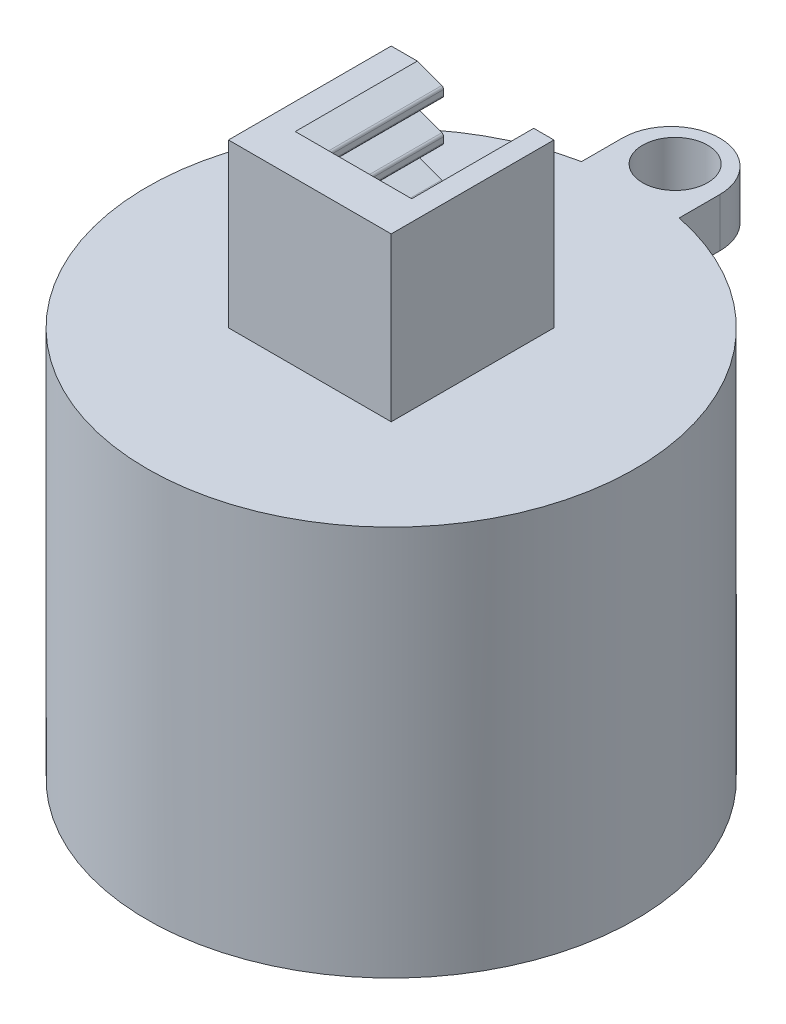
SolidWorks part; units mm, degrees
ref_plane "Front Plane" through (0, 0, 0) normal (0, 0, 1) x (1, 0, 0)
ref_plane "Top Plane" through (0, 0, 0) normal (0, 1, 0) x (1, 0, 0)
ref_plane "Right Plane" through (0, 0, 0) normal (1, 0, 0) x (0, 0, -1)
sketch "Sketch1" plane through (0, 0, 0) normal (0, 1, 0) x (1, 0, 0)
  circle A0 centre (0, 0) radius 15
  circle A1 centre (0, 0) radius 13
  dimension "D1" = 26
  dimension "D2" = 30
extrude "Boss-Extrude1" add sketch "Sketch1" along normal blind 20
sketch "Sketch2" plane through (0, 20, 0) normal (0, 1, 0) x (1, 0, 0)
  circle A0 centre (0, 0) radius 15
extrude "Boss-Extrude2" add sketch "Sketch2" along normal blind 4
sketch "Sketch4" plane through (0, 24, 0) normal (0, 1, 0) x (1, 0, 0)
  line L0 (0, 5) -> (0, -5) construction
  line L1 (-5, 5) -> (5, 5)
  line L2 (-5, 5) -> (-5, -5)
  line L3 (-5, -5) -> (5, -5)
  line L4 (5, 5) -> (5, -5)
  line L5 (-5, 0) -> (5, 0) construction
  dimension "D1" = 10
  dimension "D2" = 10
extrude "Boss-Extrude3" add sketch "Sketch4" along normal blind 10
sketch "Sketch6" plane through (0, 0, -5) normal (0, 0, -1) x (-1, 0, 0)
  line L1 (-5, 34) -> (5, 34) construction
  line L3 (-3.7584, 34) -> (3.3958, 34)
  line L4 (-3.7584, 24) -> (3.5416, 24)
  line L405 (2.1355, 274) -> (0.2416, 274)
  line L406 (0.2416, 274) -> (0.2416, 34)
  line L407 (0.2416, 34) -> (-1.7584, 34)
  line L408 (-1.7584, 34) -> (-1.7584, 274)
  line L409 (-1.7584, 274) -> (-3.7584, 274)
  line L410 (-3.7584, 274) -> (-3.7584, 24)
  line L411 (-3.7584, 24) -> (3.5416, 24)
  line L412 (3.5416, 24) -> (3.5416, 24.6743)
  line L413 (3.5416, 24.6743) -> (1.8918, 25.2748)
  line L414 (1.7816, 25.432) -> (1.7816, 25.7555)
  line L415 (1.8918, 25.9128) -> (3.5416, 26.5133)
  line L416 (3.5416, 26.5133) -> (3.5416, 27.1876)
  line L417 (3.5416, 27.1876) -> (1.8918, 27.7881)
  line L418 (1.7816, 27.9453) -> (1.7816, 28.2688)
  line L419 (1.8918, 28.426) -> (3.5416, 29.0265)
  line L420 (3.5416, 29.0265) -> (3.5416, 29.7008)
  line L421 (3.5416, 29.7008) -> (1.8918, 30.3013)
  line L422 (1.7816, 30.4586) -> (1.7816, 30.7821)
  line L423 (1.8918, 30.9393) -> (3.5416, 31.5398)
  line L424 (3.5416, 31.5398) -> (3.5416, 32.2141)
  line L425 (3.5416, 32.2141) -> (1.8918, 32.8146)
  line L426 (1.7816, 32.9719) -> (1.7816, 33.2953)
  line L427 (1.8918, 33.4526) -> (3.5416, 34.0531)
  line L428 (3.5416, 34.0531) -> (3.5416, 34.7274)
  line L429 (3.5416, 34.7274) -> (1.8918, 35.3279)
  line L430 (1.7816, 35.4851) -> (1.7816, 35.8086)
  line L431 (1.8918, 35.9658) -> (3.5416, 36.5664)
  line L432 (3.5416, 36.5664) -> (3.5416, 37.2406)
  line L433 (3.5416, 37.2406) -> (1.8918, 37.8412)
  line L434 (1.7816, 37.9984) -> (1.7816, 38.3219)
  line L435 (1.8918, 38.4791) -> (3.5416, 39.0796)
  line L436 (3.5416, 39.0796) -> (3.5416, 39.7539)
  line L437 (3.5416, 39.7539) -> (1.8918, 40.3544)
  line L438 (1.7816, 40.5117) -> (1.7816, 40.8351)
  line L439 (1.8918, 40.9924) -> (3.5416, 41.5929)
  line L440 (3.5416, 41.5929) -> (3.5416, 42.2672)
  line L441 (3.5416, 42.2672) -> (1.8918, 42.8677)
  line L442 (1.7816, 43.025) -> (1.7816, 43.3484)
  line L443 (1.8918, 43.5057) -> (3.5416, 44.1062)
  line L444 (3.5416, 44.1062) -> (3.5416, 44.7805)
  line L445 (3.5416, 44.7805) -> (1.8918, 45.381)
  line L446 (1.7816, 45.5382) -> (1.7816, 45.8617)
  line L447 (1.8918, 46.0189) -> (3.5416, 46.6194)
  line L448 (3.5416, 46.6194) -> (3.5416, 47.2937)
  line L449 (3.5416, 47.2937) -> (1.8918, 47.8942)
  line L450 (1.7816, 48.0515) -> (1.7816, 48.375)
  line L451 (1.8918, 48.5322) -> (3.5416, 49.1327)
  line L452 (3.5416, 49.1327) -> (3.5416, 49.807)
  line L453 (3.5416, 49.807) -> (1.8918, 50.4075)
  line L454 (1.7816, 50.5648) -> (1.7816, 50.8882)
  line L455 (1.8918, 51.0455) -> (3.5416, 51.646)
  line L456 (3.5416, 51.646) -> (3.5416, 52.3203)
  line L457 (3.5416, 52.3203) -> (1.8918, 52.9208)
  line L458 (1.7816, 53.078) -> (1.7816, 53.4015)
  line L459 (1.8918, 53.5588) -> (3.5416, 54.1593)
  line L460 (3.5416, 54.1593) -> (3.5416, 54.8335)
  line L461 (3.5416, 54.8335) -> (1.8918, 55.4341)
  line L462 (1.7816, 55.5913) -> (1.7816, 55.9148)
  line L463 (1.8918, 56.072) -> (3.5416, 56.6725)
  line L464 (3.5416, 56.6725) -> (3.5416, 57.3468)
  line L465 (3.5416, 57.3468) -> (1.8918, 57.9473)
  line L466 (1.7816, 58.1046) -> (1.7816, 58.428)
  line L467 (1.8918, 58.5853) -> (3.5416, 59.1858)
  line L468 (3.5416, 59.1858) -> (3.5416, 59.8601)
  line L469 (3.5416, 59.8601) -> (1.8918, 60.4606)
  line L470 (1.7816, 60.6179) -> (1.7816, 60.9413)
  line L471 (1.8918, 61.0986) -> (3.5416, 61.6991)
  line L472 (3.5416, 61.6991) -> (3.5416, 62.3734)
  line L473 (3.5416, 62.3734) -> (1.8918, 62.9739)
  line L474 (1.7816, 63.1311) -> (1.7816, 63.4546)
  line L475 (1.8918, 63.6118) -> (3.5416, 64.2124)
  line L476 (3.5416, 64.2124) -> (3.5416, 64.8866)
  line L477 (3.5416, 64.8866) -> (1.8918, 65.4871)
  line L478 (1.7816, 65.6444) -> (1.7816, 65.9679)
  line L479 (1.8918, 66.1251) -> (3.5416, 66.7256)
  line L480 (3.5416, 66.7256) -> (3.5416, 67.3999)
  line L481 (3.5416, 67.3999) -> (1.8918, 68.0004)
  line L482 (1.7816, 68.1577) -> (1.7816, 68.4811)
  line L483 (1.8918, 68.6384) -> (3.5416, 69.2389)
  line L484 (3.5416, 69.2389) -> (3.5416, 69.9132)
  line L485 (3.5416, 69.9132) -> (1.8918, 70.5137)
  line L486 (1.7816, 70.6709) -> (1.7816, 70.9944)
  line L487 (1.8918, 71.1517) -> (3.5416, 71.7522)
  line L488 (3.5416, 71.7522) -> (3.5416, 72.4265)
  line L489 (3.5416, 72.4265) -> (1.8918, 73.027)
  line L490 (1.7816, 73.1842) -> (1.7816, 73.5077)
  line L491 (1.8918, 73.6649) -> (3.5416, 74.2654)
  line L492 (3.5416, 74.2654) -> (3.5416, 74.9397)
  line L493 (3.5416, 74.9397) -> (1.8918, 75.5402)
  line L494 (1.7816, 75.6975) -> (1.7816, 76.0209)
  line L495 (1.8918, 76.1782) -> (3.5416, 76.7787)
  line L496 (3.5416, 76.7787) -> (3.5416, 77.453)
  line L497 (3.5416, 77.453) -> (1.8918, 78.0535)
  line L498 (1.7816, 78.2108) -> (1.7816, 78.5342)
  line L499 (1.8918, 78.6915) -> (3.5416, 79.292)
  line L500 (3.5416, 79.292) -> (3.5416, 79.9663)
  line L501 (3.5416, 79.9663) -> (1.8918, 80.5668)
  line L502 (1.7816, 80.724) -> (1.7816, 81.0475)
  line L503 (1.8918, 81.2047) -> (3.5416, 81.8053)
  line L504 (3.5416, 81.8053) -> (3.5416, 82.4795)
  line L505 (3.5416, 82.4795) -> (1.8918, 83.0801)
  line L506 (1.7816, 83.2373) -> (1.7816, 83.5608)
  line L507 (1.8918, 83.718) -> (3.5416, 84.3185)
  line L508 (3.5416, 84.3185) -> (3.5416, 84.9928)
  line L509 (3.5416, 84.9928) -> (1.8918, 85.5933)
  line L510 (1.7816, 85.7506) -> (1.7816, 86.074)
  line L511 (1.8918, 86.2313) -> (3.5416, 86.8318)
  line L512 (3.5416, 86.8318) -> (3.5416, 87.5061)
  line L513 (3.5416, 87.5061) -> (1.8918, 88.1066)
  line L514 (1.7816, 88.2638) -> (1.7816, 88.5873)
  line L515 (1.8918, 88.7446) -> (3.5416, 89.3451)
  line L516 (3.5416, 89.3451) -> (3.5416, 90.0194)
  line L517 (3.5416, 90.0194) -> (1.8918, 90.6199)
  line L518 (1.7816, 90.7771) -> (1.7816, 91.1006)
  line L519 (1.8918, 91.2578) -> (3.5416, 91.8583)
  line L520 (3.5416, 91.8583) -> (3.5416, 92.5326)
  line L521 (3.5416, 92.5326) -> (1.8918, 93.1331)
  line L522 (1.7816, 93.2904) -> (1.7816, 93.6139)
  line L523 (1.8918, 93.7711) -> (3.5416, 94.3716)
  line L524 (3.5416, 94.3716) -> (3.5416, 95.0459)
  line L525 (3.5416, 95.0459) -> (1.8918, 95.6464)
  line L526 (1.7816, 95.8037) -> (1.7816, 96.1271)
  line L527 (1.8918, 96.2844) -> (3.5416, 96.8849)
  line L528 (3.5416, 96.8849) -> (3.5416, 97.5592)
  line L529 (3.5416, 97.5592) -> (1.8918, 98.1597)
  line L530 (1.7816, 98.3169) -> (1.7816, 98.6404)
  line L531 (1.8918, 98.7976) -> (3.5416, 99.3982)
  line L532 (3.5416, 99.3982) -> (3.5416, 100.0724)
  line L533 (3.5416, 100.0724) -> (1.8918, 100.673)
  line L534 (1.7816, 100.8302) -> (1.7816, 101.1537)
  line L535 (1.8918, 101.3109) -> (3.5416, 101.9114)
  line L536 (3.5416, 101.9114) -> (3.5416, 102.5857)
  line L537 (3.5416, 102.5857) -> (1.8918, 103.1862)
  line L538 (1.7816, 103.3435) -> (1.7816, 103.6669)
  line L539 (1.8918, 103.8242) -> (3.5416, 104.4247)
  line L540 (3.5416, 104.4247) -> (3.5416, 105.099)
  line L541 (3.5416, 105.099) -> (1.8918, 105.6995)
  line L542 (1.7816, 105.8568) -> (1.7816, 106.1802)
  line L543 (1.8918, 106.3375) -> (3.5416, 106.938)
  line L544 (3.5416, 106.938) -> (3.5416, 107.6123)
  line L545 (3.5416, 107.6123) -> (1.8918, 108.2128)
  line L546 (1.7816, 108.37) -> (1.7816, 108.6935)
  line L547 (1.8918, 108.8507) -> (3.5416, 109.4512)
  line L548 (3.5416, 109.4512) -> (3.5416, 110.1255)
  line L549 (3.5416, 110.1255) -> (1.8918, 110.726)
  line L550 (1.7816, 110.8833) -> (1.7816, 111.2068)
  line L551 (1.8918, 111.364) -> (3.5416, 111.9645)
  line L552 (3.5416, 111.9645) -> (3.5416, 112.6388)
  line L553 (3.5416, 112.6388) -> (1.8918, 113.2393)
  line L554 (1.7816, 113.3966) -> (1.7816, 113.72)
  line L555 (1.8918, 113.8773) -> (3.5416, 114.4778)
  line L556 (3.5416, 114.4778) -> (3.5416, 115.1521)
  line L557 (3.5416, 115.1521) -> (1.8918, 115.7526)
  line L558 (1.7816, 115.9098) -> (1.7816, 116.2333)
  line L559 (1.8918, 116.3906) -> (3.5416, 116.9911)
  line L560 (3.5416, 116.9911) -> (3.5416, 117.6653)
  line L561 (3.5416, 117.6653) -> (1.8918, 118.2659)
  line L562 (1.7816, 118.4231) -> (1.7816, 118.7466)
  line L563 (1.8918, 118.9038) -> (3.5416, 119.5043)
  line L564 (3.5416, 119.5043) -> (3.5416, 120.1786)
  line L565 (3.5416, 120.1786) -> (1.8918, 120.7791)
  line L566 (1.7816, 120.9364) -> (1.7816, 121.2598)
  line L567 (1.8918, 121.4171) -> (3.5416, 122.0176)
  line L568 (3.5416, 122.0176) -> (3.5416, 122.6919)
  line L569 (3.5416, 122.6919) -> (1.8918, 123.2924)
  line L570 (1.7816, 123.4497) -> (1.7816, 123.7731)
  line L571 (1.8918, 123.9304) -> (3.5416, 124.5309)
  line L572 (3.5416, 124.5309) -> (3.5416, 125.2052)
  line L573 (3.5416, 125.2052) -> (1.8918, 125.8057)
  line L574 (1.7816, 125.9629) -> (1.7816, 126.2864)
  line L575 (1.8918, 126.4436) -> (3.5416, 127.0442)
  line L576 (3.5416, 127.0442) -> (3.5416, 127.7184)
  line L577 (3.5416, 127.7184) -> (1.8918, 128.3189)
  line L578 (1.7816, 128.4762) -> (1.7816, 128.7997)
  line L579 (1.8918, 128.9569) -> (3.5416, 129.5574)
  line L580 (3.5416, 129.5574) -> (3.5416, 130.2317)
  line L581 (3.5416, 130.2317) -> (1.8918, 130.8322)
  line L582 (1.7816, 130.9895) -> (1.7816, 131.3129)
  line L583 (1.8918, 131.4702) -> (3.5416, 132.0707)
  line L584 (3.5416, 132.0707) -> (3.5416, 132.745)
  line L585 (3.5416, 132.745) -> (1.8918, 133.3455)
  line L586 (1.7816, 133.5027) -> (1.7816, 133.8262)
  line L587 (1.8918, 133.9835) -> (3.5416, 134.584)
  line L588 (3.5416, 134.584) -> (3.5416, 135.2583)
  line L589 (3.5416, 135.2583) -> (1.8918, 135.8588)
  line L590 (1.7816, 136.016) -> (1.7816, 136.3395)
  line L591 (1.8918, 136.4967) -> (3.5416, 137.0972)
  line L592 (3.5416, 137.0972) -> (3.5416, 137.7715)
  line L593 (3.5416, 137.7715) -> (1.8918, 138.372)
  line L594 (1.7816, 138.5293) -> (1.7816, 138.8527)
  line L595 (1.8918, 139.01) -> (3.5416, 139.6105)
  line L596 (3.5416, 139.6105) -> (3.5416, 140.2848)
  line L597 (3.5416, 140.2848) -> (1.8918, 140.8853)
  line L598 (1.7816, 141.0426) -> (1.7816, 141.366)
  line L599 (1.8918, 141.5233) -> (3.5416, 142.1238)
  line L600 (3.5416, 142.1238) -> (3.5416, 142.7981)
  line L601 (3.5416, 142.7981) -> (1.8918, 143.3986)
  line L602 (1.7816, 143.5558) -> (1.7816, 143.8793)
  line L603 (1.8918, 144.0365) -> (3.5416, 144.6371)
  line L604 (3.5416, 144.6371) -> (3.5416, 145.3113)
  line L605 (3.5416, 145.3113) -> (1.8918, 145.9119)
  line L606 (1.7816, 146.0691) -> (1.7816, 146.3926)
  line L607 (1.8918, 146.5498) -> (3.5416, 147.1503)
  line L608 (3.5416, 147.1503) -> (3.5416, 147.8246)
  line L609 (3.5416, 147.8246) -> (1.8918, 148.4251)
  line L610 (1.7816, 148.5824) -> (1.7816, 148.9058)
  line L611 (1.8918, 149.0631) -> (3.5416, 149.6636)
  line L612 (3.5416, 149.6636) -> (3.5416, 150.3379)
  line L613 (3.5416, 150.3379) -> (1.8918, 150.9384)
  line L614 (1.7816, 151.0956) -> (1.7816, 151.4191)
  line L615 (1.8918, 151.5764) -> (3.5416, 152.1769)
  line L616 (3.5416, 152.1769) -> (3.5416, 152.8512)
  line L617 (3.5416, 152.8512) -> (1.8918, 153.4517)
  line L618 (1.7816, 153.6089) -> (1.7816, 153.9324)
  line L619 (1.8918, 154.0896) -> (3.5416, 154.6901)
  line L620 (3.5416, 154.6901) -> (3.5416, 155.3644)
  line L621 (3.5416, 155.3644) -> (1.8918, 155.9649)
  line L622 (1.7816, 156.1222) -> (1.7816, 156.4457)
  line L623 (1.8918, 156.6029) -> (3.5416, 157.2034)
  line L624 (3.5416, 157.2034) -> (3.5416, 157.8777)
  line L625 (3.5416, 157.8777) -> (1.8918, 158.4782)
  line L626 (1.7816, 158.6355) -> (1.7816, 158.9589)
  line L627 (1.8918, 159.1162) -> (3.5416, 159.7167)
  line L628 (3.5416, 159.7167) -> (3.5416, 160.391)
  line L629 (3.5416, 160.391) -> (1.8918, 160.9915)
  line L630 (1.7816, 161.1487) -> (1.7816, 161.4722)
  line L631 (1.8918, 161.6294) -> (3.5416, 162.23)
  line L632 (3.5416, 162.23) -> (3.5416, 162.9042)
  line L633 (3.5416, 162.9042) -> (1.8918, 163.5048)
  line L634 (1.7816, 163.662) -> (1.7816, 163.9855)
  line L635 (1.8918, 164.1427) -> (3.5416, 164.7432)
  line L636 (3.5416, 164.7432) -> (3.5416, 165.4175)
  line L637 (3.5416, 165.4175) -> (1.8918, 166.018)
  line L638 (1.7816, 166.1753) -> (1.7816, 166.4987)
  line L639 (1.8918, 166.656) -> (3.5416, 167.2565)
  line L640 (3.5416, 167.2565) -> (3.5416, 167.9308)
  line L641 (3.5416, 167.9308) -> (1.8918, 168.5313)
  line L642 (1.7816, 168.6886) -> (1.7816, 169.012)
  line L643 (1.8918, 169.1693) -> (3.5416, 169.7698)
  line L644 (3.5416, 169.7698) -> (3.5416, 170.4441)
  line L645 (3.5416, 170.4441) -> (1.8918, 171.0446)
  line L646 (1.7816, 171.2018) -> (1.7816, 171.5253)
  line L647 (1.8918, 171.6825) -> (3.5416, 172.283)
  line L648 (3.5416, 172.283) -> (3.5416, 172.9573)
  line L649 (3.5416, 172.9573) -> (1.8918, 173.5578)
  line L650 (1.7816, 173.7151) -> (1.7816, 174.0386)
  line L651 (1.8918, 174.1958) -> (3.5416, 174.7963)
  line L652 (3.5416, 174.7963) -> (3.5416, 175.4706)
  line L653 (3.5416, 175.4706) -> (1.8918, 176.0711)
  line L654 (1.7816, 176.2284) -> (1.7816, 176.5518)
  line L655 (1.8918, 176.7091) -> (3.5416, 177.3096)
  line L656 (3.5416, 177.3096) -> (3.5416, 177.9839)
  line L657 (3.5416, 177.9839) -> (1.8918, 178.5844)
  line L658 (1.7816, 178.7416) -> (1.7816, 179.0651)
  line L659 (1.8918, 179.2224) -> (3.5416, 179.8229)
  line L660 (3.5416, 179.8229) -> (3.5416, 180.4971)
  line L661 (3.5416, 180.4971) -> (1.8918, 181.0977)
  line L662 (1.7816, 181.2549) -> (1.7816, 181.5784)
  line L663 (1.8918, 181.7356) -> (3.5416, 182.3361)
  line L664 (3.5416, 182.3361) -> (3.5416, 183.0104)
  line L665 (3.5416, 183.0104) -> (1.8918, 183.6109)
  line L666 (1.7816, 183.7682) -> (1.7816, 184.0916)
  line L667 (1.8918, 184.2489) -> (3.5416, 184.8494)
  line L668 (3.5416, 184.8494) -> (3.5416, 185.5237)
  line L669 (3.5416, 185.5237) -> (1.8918, 186.1242)
  line L670 (1.7816, 186.2815) -> (1.7816, 186.6049)
  line L671 (1.8918, 186.7622) -> (3.5416, 187.3627)
  line L672 (3.5416, 187.3627) -> (3.5416, 188.037)
  line L673 (3.5416, 188.037) -> (1.8918, 188.6375)
  line L674 (1.7816, 188.7947) -> (1.7816, 189.1182)
  line L675 (1.8918, 189.2754) -> (3.5416, 189.876)
  line L676 (3.5416, 189.876) -> (3.5416, 190.5502)
  line L677 (3.5416, 190.5502) -> (1.8918, 191.1507)
  line L678 (1.7816, 191.308) -> (1.7816, 191.6315)
  line L679 (1.8918, 191.7887) -> (3.5416, 192.3892)
  line L680 (3.5416, 192.3892) -> (3.5416, 193.0635)
  line L681 (3.5416, 193.0635) -> (1.8918, 193.664)
  line L682 (1.7816, 193.8213) -> (1.7816, 194.1447)
  line L683 (1.8918, 194.302) -> (3.5416, 194.9025)
  line L684 (3.5416, 194.9025) -> (3.5416, 195.5768)
  line L685 (3.5416, 195.5768) -> (1.8918, 196.1773)
  line L686 (1.7816, 196.3345) -> (1.7816, 196.658)
  line L687 (1.8918, 196.8153) -> (3.5416, 197.4158)
  line L688 (3.5416, 197.4158) -> (3.5416, 198.0901)
  line L689 (3.5416, 198.0901) -> (1.8918, 198.6906)
  line L690 (1.7816, 198.8478) -> (1.7816, 199.1713)
  line L691 (1.8918, 199.3285) -> (3.5416, 199.929)
  line L692 (3.5416, 199.929) -> (3.5416, 200.6033)
  line L693 (3.5416, 200.6033) -> (1.8918, 201.2038)
  line L694 (1.7816, 201.3611) -> (1.7816, 201.6845)
  line L695 (1.8918, 201.8418) -> (3.5416, 202.4423)
  line L696 (3.5416, 202.4423) -> (3.5416, 203.1166)
  line L697 (3.5416, 203.1166) -> (1.8918, 203.7171)
  line L698 (1.7816, 203.8744) -> (1.7816, 204.1978)
  line L699 (1.8918, 204.3551) -> (3.5416, 204.9556)
  line L700 (3.5416, 204.9556) -> (3.5416, 205.6299)
  line L701 (3.5416, 205.6299) -> (1.8918, 206.2304)
  line L702 (1.7816, 206.3876) -> (1.7816, 206.7111)
  line L703 (1.8918, 206.8683) -> (3.5416, 207.4689)
  line L704 (3.5416, 207.4689) -> (3.5416, 208.1431)
  line L705 (3.5416, 208.1431) -> (1.8918, 208.7437)
  line L706 (1.7816, 208.9009) -> (1.7816, 209.2244)
  line L707 (1.8918, 209.3816) -> (3.5416, 209.9821)
  line L708 (3.5416, 209.9821) -> (3.5416, 210.6564)
  line L709 (3.5416, 210.6564) -> (1.8918, 211.2569)
  line L710 (1.7816, 211.4142) -> (1.7816, 211.7376)
  line L711 (1.8918, 211.8949) -> (3.5416, 212.4954)
  line L712 (3.5416, 212.4954) -> (3.5416, 213.1697)
  line L713 (3.5416, 213.1697) -> (1.8918, 213.7702)
  line L714 (1.7816, 213.9274) -> (1.7816, 214.2509)
  line L715 (1.8918, 214.4082) -> (3.5416, 215.0087)
  line L716 (3.5416, 215.0087) -> (3.5416, 215.683)
  line L717 (3.5416, 215.683) -> (1.8918, 216.2835)
  line L718 (1.7816, 216.4407) -> (1.7816, 216.7642)
  line L719 (1.8918, 216.9214) -> (3.5416, 217.5219)
  line L720 (3.5416, 217.5219) -> (3.5416, 218.1962)
  line L721 (3.5416, 218.1962) -> (1.8918, 218.7967)
  line L722 (1.7816, 218.954) -> (1.7816, 219.2775)
  line L723 (1.8918, 219.4347) -> (3.5416, 220.0352)
  line L724 (3.5416, 220.0352) -> (3.5416, 220.7095)
  line L725 (3.5416, 220.7095) -> (1.8918, 221.31)
  line L726 (1.7816, 221.4673) -> (1.7816, 221.7907)
  line L727 (1.8918, 221.948) -> (3.5416, 222.5485)
  line L728 (3.5416, 222.5485) -> (3.5416, 223.2228)
  line L729 (3.5416, 223.2228) -> (1.8918, 223.8233)
  line L730 (1.7816, 223.9805) -> (1.7816, 224.304)
  line L731 (1.8918, 224.4612) -> (3.5416, 225.0618)
  line L732 (3.5416, 225.0618) -> (3.5416, 225.736)
  line L733 (3.5416, 225.736) -> (1.8918, 226.3366)
  line L734 (1.7816, 226.4938) -> (1.7816, 226.8173)
  line L735 (1.8918, 226.9745) -> (3.5416, 227.575)
  line L736 (3.5416, 227.575) -> (3.5416, 228.2493)
  line L737 (3.5416, 228.2493) -> (1.8918, 228.8498)
  line L738 (1.7816, 229.0071) -> (1.7816, 229.3305)
  line L739 (1.8918, 229.4878) -> (3.5416, 230.0883)
  line L740 (3.5416, 230.0883) -> (3.5416, 230.7626)
  line L741 (3.5416, 230.7626) -> (1.8918, 231.3631)
  line L742 (1.7816, 231.5204) -> (1.7816, 231.8438)
  line L743 (1.8918, 232.0011) -> (3.5416, 232.6016)
  line L744 (3.5416, 232.6016) -> (3.5416, 233.2759)
  line L745 (3.5416, 233.2759) -> (1.8918, 233.8764)
  line L746 (1.7816, 234.0336) -> (1.7816, 234.3571)
  line L747 (1.8918, 234.5143) -> (3.5416, 235.1148)
  line L748 (3.5416, 235.1148) -> (3.5416, 235.7891)
  line L749 (3.5416, 235.7891) -> (1.8918, 236.3896)
  line L750 (1.7816, 236.5469) -> (1.7816, 236.8704)
  line L751 (1.8918, 237.0276) -> (3.5416, 237.6281)
  line L752 (3.5416, 237.6281) -> (3.5416, 238.3024)
  line L753 (3.5416, 238.3024) -> (1.8918, 238.9029)
  line L754 (1.7816, 239.0602) -> (1.7816, 239.3836)
  line L755 (1.8918, 239.5409) -> (3.5416, 240.1414)
  line L756 (3.5416, 240.1414) -> (3.5416, 240.8157)
  line L757 (3.5416, 240.8157) -> (1.8918, 241.4162)
  line L758 (1.7816, 241.5734) -> (1.7816, 241.8969)
  line L759 (1.8918, 242.0542) -> (3.5416, 242.6547)
  line L760 (3.5416, 242.6547) -> (3.5416, 243.3289)
  line L761 (3.5416, 243.3289) -> (1.8918, 243.9295)
  line L762 (1.7816, 244.0867) -> (1.7816, 244.4102)
  line L763 (1.8918, 244.5674) -> (3.5416, 245.1679)
  line L764 (3.5416, 245.1679) -> (3.5416, 245.8422)
  line L765 (3.5416, 245.8422) -> (1.8918, 246.4427)
  line L766 (1.7816, 246.6) -> (1.7816, 246.9234)
  line L767 (1.8918, 247.0807) -> (3.5416, 247.6812)
  line L768 (3.5416, 247.6812) -> (3.5416, 248.3555)
  line L769 (3.5416, 248.3555) -> (1.8918, 248.956)
  line L770 (1.7816, 249.1133) -> (1.7816, 249.4367)
  line L771 (1.8918, 249.594) -> (3.5416, 250.1945)
  line L772 (3.5416, 250.1945) -> (3.5416, 250.8688)
  line L773 (3.5416, 250.8688) -> (1.8918, 251.4693)
  line L774 (1.7816, 251.6265) -> (1.7816, 251.95)
  line L775 (1.8918, 252.1072) -> (3.5416, 252.7078)
  line L776 (3.5416, 252.7078) -> (3.5416, 253.382)
  line L777 (3.5416, 253.382) -> (1.8918, 253.9825)
  line L778 (1.7816, 254.1398) -> (1.7816, 254.4633)
  line L779 (1.8918, 254.6205) -> (3.5416, 255.221)
  line L780 (3.5416, 255.221) -> (3.5416, 255.8953)
  line L781 (3.5416, 255.8953) -> (1.8918, 256.4958)
  line L782 (1.7816, 256.6531) -> (1.7816, 256.9765)
  line L783 (1.8918, 257.1338) -> (3.5416, 257.7343)
  line L784 (3.5416, 257.7343) -> (3.5416, 258.4086)
  line L785 (3.5416, 258.4086) -> (1.8918, 259.0091)
  line L786 (1.7816, 259.1663) -> (1.7816, 259.4898)
  line L787 (1.8918, 259.6471) -> (3.5416, 260.2476)
  line L788 (3.5416, 260.2476) -> (3.5416, 260.9219)
  line L789 (3.5416, 260.9219) -> (1.8918, 261.5224)
  line L790 (1.7816, 261.6796) -> (1.7816, 262.0031)
  line L791 (1.8918, 262.1603) -> (3.5416, 262.7608)
  line L792 (3.5416, 262.7608) -> (3.5416, 263.4351)
  line L793 (3.5416, 263.4351) -> (1.8918, 264.0356)
  line L794 (1.7816, 264.1929) -> (1.7816, 264.5163)
  line L795 (1.8918, 264.6736) -> (3.5416, 265.2741)
  line L796 (3.5416, 265.2741) -> (3.5416, 265.9484)
  line L797 (3.5416, 265.9484) -> (1.8918, 266.5489)
  line L798 (1.7816, 266.7062) -> (1.7816, 267.0296)
  line L799 (1.8918, 267.1869) -> (3.5416, 267.7874)
  line L800 (3.5416, 267.7874) -> (3.5416, 268.4617)
  line L801 (3.5416, 268.4617) -> (1.8918, 269.0622)
  line L802 (1.7816, 269.2194) -> (1.7816, 269.5429)
  line L803 (1.8918, 269.7001) -> (3.5416, 270.3007)
  line L804 (3.5416, 270.3007) -> (3.5416, 270.9749)
  line L805 (3.5416, 270.9749) -> (1.8918, 271.5755)
  line L806 (1.7816, 271.7327) -> (1.7816, 272.0562)
  line L807 (1.8918, 272.2134) -> (3.5416, 272.8139)
  line L808 (3.5416, 272.8139) -> (3.5416, 273.4882)
  line L809 (3.5416, 273.4882) -> (2.1355, 274)
  line L815 (-3.7584, 34) -> (-3.7584, 24)
  line L816 (-3.7584, 24) -> (3.5416, 24)
  line L817 (3.5416, 24) -> (3.5416, 24.6743)
  line L818 (3.5416, 24.6743) -> (1.8918, 25.2748)
  line L819 (1.7816, 25.432) -> (1.7816, 25.7555)
  line L820 (1.8918, 25.9128) -> (3.5416, 26.5133)
  line L821 (3.5416, 26.5133) -> (3.5416, 27.1876)
  line L822 (3.5416, 27.1876) -> (1.8918, 27.7881)
  line L823 (1.7816, 27.9453) -> (1.7816, 28.2688)
  line L824 (1.8918, 28.426) -> (3.5416, 29.0265)
  line L825 (3.5416, 29.0265) -> (3.5416, 29.7008)
  line L826 (3.5416, 29.7008) -> (1.8918, 30.3013)
  line L827 (1.7816, 30.4586) -> (1.7816, 30.7821)
  line L828 (1.8918, 30.9393) -> (3.5416, 31.5398)
  line L829 (3.5416, 31.5398) -> (3.5416, 32.2141)
  line L830 (3.5416, 32.2141) -> (1.8918, 32.8146)
  line L831 (1.7816, 32.9719) -> (1.7816, 33.2953)
  line L832 (1.8918, 33.4526) -> (3.3958, 34)
  arc A198 (1.7816, 25.432) -> (1.8918, 25.2748) centre (1.949, 25.432) ccw
  arc A199 (1.8918, 25.9128) -> (1.7816, 25.7555) centre (1.949, 25.7555) ccw
  arc A200 (1.7816, 27.9453) -> (1.8918, 27.7881) centre (1.949, 27.9453) ccw
  arc A201 (1.8918, 28.426) -> (1.7816, 28.2688) centre (1.949, 28.2688) ccw
  arc A202 (1.7816, 30.4586) -> (1.8918, 30.3013) centre (1.949, 30.4586) ccw
  arc A203 (1.8918, 30.9393) -> (1.7816, 30.7821) centre (1.949, 30.7821) ccw
  arc A204 (1.7816, 32.9719) -> (1.8918, 32.8146) centre (1.949, 32.9719) ccw
  arc A205 (1.8918, 33.4526) -> (1.7816, 33.2953) centre (1.949, 33.2953) ccw
  arc A206 (1.7816, 35.4851) -> (1.8918, 35.3279) centre (1.949, 35.4851) ccw
  arc A207 (1.8918, 35.9658) -> (1.7816, 35.8086) centre (1.949, 35.8086) ccw
  arc A208 (1.7816, 37.9984) -> (1.8918, 37.8412) centre (1.949, 37.9984) ccw
  arc A209 (1.8918, 38.4791) -> (1.7816, 38.3219) centre (1.949, 38.3219) ccw
  arc A210 (1.7816, 40.5117) -> (1.8918, 40.3544) centre (1.949, 40.5117) ccw
  arc A211 (1.8918, 40.9924) -> (1.7816, 40.8351) centre (1.949, 40.8351) ccw
  arc A212 (1.7816, 43.025) -> (1.8918, 42.8677) centre (1.949, 43.025) ccw
  arc A213 (1.8918, 43.5057) -> (1.7816, 43.3484) centre (1.949, 43.3484) ccw
  arc A214 (1.7816, 45.5382) -> (1.8918, 45.381) centre (1.949, 45.5382) ccw
  arc A215 (1.8918, 46.0189) -> (1.7816, 45.8617) centre (1.949, 45.8617) ccw
  arc A216 (1.7816, 48.0515) -> (1.8918, 47.8942) centre (1.949, 48.0515) ccw
  arc A217 (1.8918, 48.5322) -> (1.7816, 48.375) centre (1.949, 48.375) ccw
  arc A218 (1.7816, 50.5648) -> (1.8918, 50.4075) centre (1.949, 50.5648) ccw
  arc A219 (1.8918, 51.0455) -> (1.7816, 50.8882) centre (1.949, 50.8882) ccw
  arc A220 (1.7816, 53.078) -> (1.8918, 52.9208) centre (1.949, 53.078) ccw
  arc A221 (1.8918, 53.5588) -> (1.7816, 53.4015) centre (1.949, 53.4015) ccw
  arc A222 (1.7816, 55.5913) -> (1.8918, 55.4341) centre (1.949, 55.5913) ccw
  arc A223 (1.8918, 56.072) -> (1.7816, 55.9148) centre (1.949, 55.9148) ccw
  arc A224 (1.7816, 58.1046) -> (1.8918, 57.9473) centre (1.949, 58.1046) ccw
  arc A225 (1.8918, 58.5853) -> (1.7816, 58.428) centre (1.949, 58.428) ccw
  arc A226 (1.7816, 60.6179) -> (1.8918, 60.4606) centre (1.949, 60.6179) ccw
  arc A227 (1.8918, 61.0986) -> (1.7816, 60.9413) centre (1.949, 60.9413) ccw
  arc A228 (1.7816, 63.1311) -> (1.8918, 62.9739) centre (1.949, 63.1311) ccw
  arc A229 (1.8918, 63.6118) -> (1.7816, 63.4546) centre (1.949, 63.4546) ccw
  arc A230 (1.7816, 65.6444) -> (1.8918, 65.4871) centre (1.949, 65.6444) ccw
  arc A231 (1.8918, 66.1251) -> (1.7816, 65.9679) centre (1.949, 65.9679) ccw
  arc A232 (1.7816, 68.1577) -> (1.8918, 68.0004) centre (1.949, 68.1577) ccw
  arc A233 (1.8918, 68.6384) -> (1.7816, 68.4811) centre (1.949, 68.4811) ccw
  arc A234 (1.7816, 70.6709) -> (1.8918, 70.5137) centre (1.949, 70.6709) ccw
  arc A235 (1.8918, 71.1517) -> (1.7816, 70.9944) centre (1.949, 70.9944) ccw
  arc A236 (1.7816, 73.1842) -> (1.8918, 73.027) centre (1.949, 73.1842) ccw
  arc A237 (1.8918, 73.6649) -> (1.7816, 73.5077) centre (1.949, 73.5077) ccw
  arc A238 (1.7816, 75.6975) -> (1.8918, 75.5402) centre (1.949, 75.6975) ccw
  arc A239 (1.8918, 76.1782) -> (1.7816, 76.0209) centre (1.949, 76.0209) ccw
  arc A240 (1.7816, 78.2108) -> (1.8918, 78.0535) centre (1.949, 78.2108) ccw
  arc A241 (1.8918, 78.6915) -> (1.7816, 78.5342) centre (1.949, 78.5342) ccw
  arc A242 (1.7816, 80.724) -> (1.8918, 80.5668) centre (1.949, 80.724) ccw
  arc A243 (1.8918, 81.2047) -> (1.7816, 81.0475) centre (1.949, 81.0475) ccw
  arc A244 (1.7816, 83.2373) -> (1.8918, 83.0801) centre (1.949, 83.2373) ccw
  arc A245 (1.8918, 83.718) -> (1.7816, 83.5608) centre (1.949, 83.5608) ccw
  arc A246 (1.7816, 85.7506) -> (1.8918, 85.5933) centre (1.949, 85.7506) ccw
  arc A247 (1.8918, 86.2313) -> (1.7816, 86.074) centre (1.949, 86.074) ccw
  arc A248 (1.7816, 88.2638) -> (1.8918, 88.1066) centre (1.949, 88.2638) ccw
  arc A249 (1.8918, 88.7446) -> (1.7816, 88.5873) centre (1.949, 88.5873) ccw
  arc A250 (1.7816, 90.7771) -> (1.8918, 90.6199) centre (1.949, 90.7771) ccw
  arc A251 (1.8918, 91.2578) -> (1.7816, 91.1006) centre (1.949, 91.1006) ccw
  arc A252 (1.7816, 93.2904) -> (1.8918, 93.1331) centre (1.949, 93.2904) ccw
  arc A253 (1.8918, 93.7711) -> (1.7816, 93.6139) centre (1.949, 93.6139) ccw
  arc A254 (1.7816, 95.8037) -> (1.8918, 95.6464) centre (1.949, 95.8037) ccw
  arc A255 (1.8918, 96.2844) -> (1.7816, 96.1271) centre (1.949, 96.1271) ccw
  arc A256 (1.7816, 98.3169) -> (1.8918, 98.1597) centre (1.949, 98.3169) ccw
  arc A257 (1.8918, 98.7976) -> (1.7816, 98.6404) centre (1.949, 98.6404) ccw
  arc A258 (1.7816, 100.8302) -> (1.8918, 100.673) centre (1.949, 100.8302) ccw
  arc A259 (1.8918, 101.3109) -> (1.7816, 101.1537) centre (1.949, 101.1537) ccw
  arc A260 (1.7816, 103.3435) -> (1.8918, 103.1862) centre (1.949, 103.3435) ccw
  arc A261 (1.8918, 103.8242) -> (1.7816, 103.6669) centre (1.949, 103.6669) ccw
  arc A262 (1.7816, 105.8568) -> (1.8918, 105.6995) centre (1.949, 105.8568) ccw
  arc A263 (1.8918, 106.3375) -> (1.7816, 106.1802) centre (1.949, 106.1802) ccw
  arc A264 (1.7816, 108.37) -> (1.8918, 108.2128) centre (1.949, 108.37) ccw
  arc A265 (1.8918, 108.8507) -> (1.7816, 108.6935) centre (1.949, 108.6935) ccw
  arc A266 (1.7816, 110.8833) -> (1.8918, 110.726) centre (1.949, 110.8833) ccw
  arc A267 (1.8918, 111.364) -> (1.7816, 111.2068) centre (1.949, 111.2068) ccw
  arc A268 (1.7816, 113.3966) -> (1.8918, 113.2393) centre (1.949, 113.3966) ccw
  arc A269 (1.8918, 113.8773) -> (1.7816, 113.72) centre (1.949, 113.72) ccw
  arc A270 (1.7816, 115.9098) -> (1.8918, 115.7526) centre (1.949, 115.9098) ccw
  arc A271 (1.8918, 116.3906) -> (1.7816, 116.2333) centre (1.949, 116.2333) ccw
  arc A272 (1.7816, 118.4231) -> (1.8918, 118.2659) centre (1.949, 118.4231) ccw
  arc A273 (1.8918, 118.9038) -> (1.7816, 118.7466) centre (1.949, 118.7466) ccw
  arc A274 (1.7816, 120.9364) -> (1.8918, 120.7791) centre (1.949, 120.9364) ccw
  arc A275 (1.8918, 121.4171) -> (1.7816, 121.2598) centre (1.949, 121.2598) ccw
  arc A276 (1.7816, 123.4497) -> (1.8918, 123.2924) centre (1.949, 123.4497) ccw
  arc A277 (1.8918, 123.9304) -> (1.7816, 123.7731) centre (1.949, 123.7731) ccw
  arc A278 (1.7816, 125.9629) -> (1.8918, 125.8057) centre (1.949, 125.9629) ccw
  arc A279 (1.8918, 126.4436) -> (1.7816, 126.2864) centre (1.949, 126.2864) ccw
  arc A280 (1.7816, 128.4762) -> (1.8918, 128.3189) centre (1.949, 128.4762) ccw
  arc A281 (1.8918, 128.9569) -> (1.7816, 128.7997) centre (1.949, 128.7997) ccw
  arc A282 (1.7816, 130.9895) -> (1.8918, 130.8322) centre (1.949, 130.9895) ccw
  arc A283 (1.8918, 131.4702) -> (1.7816, 131.3129) centre (1.949, 131.3129) ccw
  arc A284 (1.7816, 133.5027) -> (1.8918, 133.3455) centre (1.949, 133.5027) ccw
  arc A285 (1.8918, 133.9835) -> (1.7816, 133.8262) centre (1.949, 133.8262) ccw
  arc A286 (1.7816, 136.016) -> (1.8918, 135.8588) centre (1.949, 136.016) ccw
  arc A287 (1.8918, 136.4967) -> (1.7816, 136.3395) centre (1.949, 136.3395) ccw
  arc A288 (1.7816, 138.5293) -> (1.8918, 138.372) centre (1.949, 138.5293) ccw
  arc A289 (1.8918, 139.01) -> (1.7816, 138.8527) centre (1.949, 138.8527) ccw
  arc A290 (1.7816, 141.0426) -> (1.8918, 140.8853) centre (1.949, 141.0426) ccw
  arc A291 (1.8918, 141.5233) -> (1.7816, 141.366) centre (1.949, 141.366) ccw
  arc A292 (1.7816, 143.5558) -> (1.8918, 143.3986) centre (1.949, 143.5558) ccw
  arc A293 (1.8918, 144.0365) -> (1.7816, 143.8793) centre (1.949, 143.8793) ccw
  arc A294 (1.7816, 146.0691) -> (1.8918, 145.9119) centre (1.949, 146.0691) ccw
  arc A295 (1.8918, 146.5498) -> (1.7816, 146.3926) centre (1.949, 146.3926) ccw
  arc A296 (1.7816, 148.5824) -> (1.8918, 148.4251) centre (1.949, 148.5824) ccw
  arc A297 (1.8918, 149.0631) -> (1.7816, 148.9058) centre (1.949, 148.9058) ccw
  arc A298 (1.7816, 151.0956) -> (1.8918, 150.9384) centre (1.949, 151.0956) ccw
  arc A299 (1.8918, 151.5764) -> (1.7816, 151.4191) centre (1.949, 151.4191) ccw
  arc A300 (1.7816, 153.6089) -> (1.8918, 153.4517) centre (1.949, 153.6089) ccw
  arc A301 (1.8918, 154.0896) -> (1.7816, 153.9324) centre (1.949, 153.9324) ccw
  arc A302 (1.7816, 156.1222) -> (1.8918, 155.9649) centre (1.949, 156.1222) ccw
  arc A303 (1.8918, 156.6029) -> (1.7816, 156.4457) centre (1.949, 156.4457) ccw
  arc A304 (1.7816, 158.6355) -> (1.8918, 158.4782) centre (1.949, 158.6355) ccw
  arc A305 (1.8918, 159.1162) -> (1.7816, 158.9589) centre (1.949, 158.9589) ccw
  arc A306 (1.7816, 161.1487) -> (1.8918, 160.9915) centre (1.949, 161.1487) ccw
  arc A307 (1.8918, 161.6294) -> (1.7816, 161.4722) centre (1.949, 161.4722) ccw
  arc A308 (1.7816, 163.662) -> (1.8918, 163.5048) centre (1.949, 163.662) ccw
  arc A309 (1.8918, 164.1427) -> (1.7816, 163.9855) centre (1.949, 163.9855) ccw
  arc A310 (1.7816, 166.1753) -> (1.8918, 166.018) centre (1.949, 166.1753) ccw
  arc A311 (1.8918, 166.656) -> (1.7816, 166.4987) centre (1.949, 166.4987) ccw
  arc A312 (1.7816, 168.6886) -> (1.8918, 168.5313) centre (1.949, 168.6886) ccw
  arc A313 (1.8918, 169.1693) -> (1.7816, 169.012) centre (1.949, 169.012) ccw
  arc A314 (1.7816, 171.2018) -> (1.8918, 171.0446) centre (1.949, 171.2018) ccw
  arc A315 (1.8918, 171.6825) -> (1.7816, 171.5253) centre (1.949, 171.5253) ccw
  arc A316 (1.7816, 173.7151) -> (1.8918, 173.5578) centre (1.949, 173.7151) ccw
  arc A317 (1.8918, 174.1958) -> (1.7816, 174.0386) centre (1.949, 174.0386) ccw
  arc A318 (1.7816, 176.2284) -> (1.8918, 176.0711) centre (1.949, 176.2284) ccw
  arc A319 (1.8918, 176.7091) -> (1.7816, 176.5518) centre (1.949, 176.5518) ccw
  arc A320 (1.7816, 178.7416) -> (1.8918, 178.5844) centre (1.949, 178.7416) ccw
  arc A321 (1.8918, 179.2224) -> (1.7816, 179.0651) centre (1.949, 179.0651) ccw
  arc A322 (1.7816, 181.2549) -> (1.8918, 181.0977) centre (1.949, 181.2549) ccw
  arc A323 (1.8918, 181.7356) -> (1.7816, 181.5784) centre (1.949, 181.5784) ccw
  arc A324 (1.7816, 183.7682) -> (1.8918, 183.6109) centre (1.949, 183.7682) ccw
  arc A325 (1.8918, 184.2489) -> (1.7816, 184.0916) centre (1.949, 184.0916) ccw
  arc A326 (1.7816, 186.2815) -> (1.8918, 186.1242) centre (1.949, 186.2815) ccw
  arc A327 (1.8918, 186.7622) -> (1.7816, 186.6049) centre (1.949, 186.6049) ccw
  arc A328 (1.7816, 188.7947) -> (1.8918, 188.6375) centre (1.949, 188.7947) ccw
  arc A329 (1.8918, 189.2754) -> (1.7816, 189.1182) centre (1.949, 189.1182) ccw
  arc A330 (1.7816, 191.308) -> (1.8918, 191.1507) centre (1.949, 191.308) ccw
  arc A331 (1.8918, 191.7887) -> (1.7816, 191.6315) centre (1.949, 191.6315) ccw
  arc A332 (1.7816, 193.8213) -> (1.8918, 193.664) centre (1.949, 193.8213) ccw
  arc A333 (1.8918, 194.302) -> (1.7816, 194.1447) centre (1.949, 194.1447) ccw
  arc A334 (1.7816, 196.3345) -> (1.8918, 196.1773) centre (1.949, 196.3345) ccw
  arc A335 (1.8918, 196.8153) -> (1.7816, 196.658) centre (1.949, 196.658) ccw
  arc A336 (1.7816, 198.8478) -> (1.8918, 198.6906) centre (1.949, 198.8478) ccw
  arc A337 (1.8918, 199.3285) -> (1.7816, 199.1713) centre (1.949, 199.1713) ccw
  arc A338 (1.7816, 201.3611) -> (1.8918, 201.2038) centre (1.949, 201.3611) ccw
  arc A339 (1.8918, 201.8418) -> (1.7816, 201.6845) centre (1.949, 201.6845) ccw
  arc A340 (1.7816, 203.8744) -> (1.8918, 203.7171) centre (1.949, 203.8744) ccw
  arc A341 (1.8918, 204.3551) -> (1.7816, 204.1978) centre (1.949, 204.1978) ccw
  arc A342 (1.7816, 206.3876) -> (1.8918, 206.2304) centre (1.949, 206.3876) ccw
  arc A343 (1.8918, 206.8683) -> (1.7816, 206.7111) centre (1.949, 206.7111) ccw
  arc A344 (1.7816, 208.9009) -> (1.8918, 208.7437) centre (1.949, 208.9009) ccw
  arc A345 (1.8918, 209.3816) -> (1.7816, 209.2244) centre (1.949, 209.2244) ccw
  arc A346 (1.7816, 211.4142) -> (1.8918, 211.2569) centre (1.949, 211.4142) ccw
  arc A347 (1.8918, 211.8949) -> (1.7816, 211.7376) centre (1.949, 211.7376) ccw
  arc A348 (1.7816, 213.9274) -> (1.8918, 213.7702) centre (1.949, 213.9274) ccw
  arc A349 (1.8918, 214.4082) -> (1.7816, 214.2509) centre (1.949, 214.2509) ccw
  arc A350 (1.7816, 216.4407) -> (1.8918, 216.2835) centre (1.949, 216.4407) ccw
  arc A351 (1.8918, 216.9214) -> (1.7816, 216.7642) centre (1.949, 216.7642) ccw
  arc A352 (1.7816, 218.954) -> (1.8918, 218.7967) centre (1.949, 218.954) ccw
  arc A353 (1.8918, 219.4347) -> (1.7816, 219.2775) centre (1.949, 219.2775) ccw
  arc A354 (1.7816, 221.4673) -> (1.8918, 221.31) centre (1.949, 221.4673) ccw
  arc A355 (1.8918, 221.948) -> (1.7816, 221.7907) centre (1.949, 221.7907) ccw
  arc A356 (1.7816, 223.9805) -> (1.8918, 223.8233) centre (1.949, 223.9805) ccw
  arc A357 (1.8918, 224.4612) -> (1.7816, 224.304) centre (1.949, 224.304) ccw
  arc A358 (1.7816, 226.4938) -> (1.8918, 226.3366) centre (1.949, 226.4938) ccw
  arc A359 (1.8918, 226.9745) -> (1.7816, 226.8173) centre (1.949, 226.8173) ccw
  arc A360 (1.7816, 229.0071) -> (1.8918, 228.8498) centre (1.949, 229.0071) ccw
  arc A361 (1.8918, 229.4878) -> (1.7816, 229.3305) centre (1.949, 229.3305) ccw
  arc A362 (1.7816, 231.5204) -> (1.8918, 231.3631) centre (1.949, 231.5204) ccw
  arc A363 (1.8918, 232.0011) -> (1.7816, 231.8438) centre (1.949, 231.8438) ccw
  arc A364 (1.7816, 234.0336) -> (1.8918, 233.8764) centre (1.949, 234.0336) ccw
  arc A365 (1.8918, 234.5143) -> (1.7816, 234.3571) centre (1.949, 234.3571) ccw
  arc A366 (1.7816, 236.5469) -> (1.8918, 236.3896) centre (1.949, 236.5469) ccw
  arc A367 (1.8918, 237.0276) -> (1.7816, 236.8704) centre (1.949, 236.8704) ccw
  arc A368 (1.7816, 239.0602) -> (1.8918, 238.9029) centre (1.949, 239.0602) ccw
  arc A369 (1.8918, 239.5409) -> (1.7816, 239.3836) centre (1.949, 239.3836) ccw
  arc A370 (1.7816, 241.5734) -> (1.8918, 241.4162) centre (1.949, 241.5734) ccw
  arc A371 (1.8918, 242.0542) -> (1.7816, 241.8969) centre (1.949, 241.8969) ccw
  arc A372 (1.7816, 244.0867) -> (1.8918, 243.9295) centre (1.949, 244.0867) ccw
  arc A373 (1.8918, 244.5674) -> (1.7816, 244.4102) centre (1.949, 244.4102) ccw
  arc A374 (1.7816, 246.6) -> (1.8918, 246.4427) centre (1.949, 246.6) ccw
  arc A375 (1.8918, 247.0807) -> (1.7816, 246.9234) centre (1.949, 246.9234) ccw
  arc A376 (1.7816, 249.1133) -> (1.8918, 248.956) centre (1.949, 249.1133) ccw
  arc A377 (1.8918, 249.594) -> (1.7816, 249.4367) centre (1.949, 249.4367) ccw
  arc A378 (1.7816, 251.6265) -> (1.8918, 251.4693) centre (1.949, 251.6265) ccw
  arc A379 (1.8918, 252.1072) -> (1.7816, 251.95) centre (1.949, 251.95) ccw
  arc A380 (1.7816, 254.1398) -> (1.8918, 253.9825) centre (1.949, 254.1398) ccw
  arc A381 (1.8918, 254.6205) -> (1.7816, 254.4633) centre (1.949, 254.4633) ccw
  arc A382 (1.7816, 256.6531) -> (1.8918, 256.4958) centre (1.949, 256.6531) ccw
  arc A383 (1.8918, 257.1338) -> (1.7816, 256.9765) centre (1.949, 256.9765) ccw
  arc A384 (1.7816, 259.1663) -> (1.8918, 259.0091) centre (1.949, 259.1663) ccw
  arc A385 (1.8918, 259.6471) -> (1.7816, 259.4898) centre (1.949, 259.4898) ccw
  arc A386 (1.7816, 261.6796) -> (1.8918, 261.5224) centre (1.949, 261.6796) ccw
  arc A387 (1.8918, 262.1603) -> (1.7816, 262.0031) centre (1.949, 262.0031) ccw
  arc A388 (1.7816, 264.1929) -> (1.8918, 264.0356) centre (1.949, 264.1929) ccw
  arc A389 (1.8918, 264.6736) -> (1.7816, 264.5163) centre (1.949, 264.5163) ccw
  arc A390 (1.7816, 266.7062) -> (1.8918, 266.5489) centre (1.949, 266.7062) ccw
  arc A391 (1.8918, 267.1869) -> (1.7816, 267.0296) centre (1.949, 267.0296) ccw
  arc A392 (1.7816, 269.2194) -> (1.8918, 269.0622) centre (1.949, 269.2194) ccw
  arc A393 (1.8918, 269.7001) -> (1.7816, 269.5429) centre (1.949, 269.5429) ccw
  arc A394 (1.7816, 271.7327) -> (1.8918, 271.5755) centre (1.949, 271.7327) ccw
  arc A395 (1.8918, 272.2134) -> (1.7816, 272.0562) centre (1.949, 272.0562) ccw
  arc A396 (1.7816, 25.432) -> (1.8918, 25.2748) centre (1.949, 25.432) ccw
  arc A397 (1.8918, 25.9128) -> (1.7816, 25.7555) centre (1.949, 25.7555) ccw
  arc A398 (1.7816, 27.9453) -> (1.8918, 27.7881) centre (1.949, 27.9453) ccw
  arc A399 (1.8918, 28.426) -> (1.7816, 28.2688) centre (1.949, 28.2688) ccw
  arc A400 (1.7816, 30.4586) -> (1.8918, 30.3013) centre (1.949, 30.4586) ccw
  arc A401 (1.8918, 30.9393) -> (1.7816, 30.7821) centre (1.949, 30.7821) ccw
  arc A402 (1.7816, 32.9719) -> (1.8918, 32.8146) centre (1.949, 32.9719) ccw
  arc A403 (1.8918, 33.4526) -> (1.7816, 33.2953) centre (1.949, 33.2953) ccw
  line M606 (-5, 24) -> (5, 24)
  line M608 (5, 34) -> (-5, 34)
  dimension "D1" = 0
extrude "Cut-Extrude2" cut sketch "Sketch6" against normal blind 7.5 contours A403 L832 L815 L817 L818 A396 L819 A397 L820 L821 L822 A398 L823 A399 L824 L825 L826 A400 L827 A401 L828 L829 L830 A402 L831 M608 M606 region at (0.4899, 28.9529, -5)
ref_plane "Plane2" through (0, 0, -15) normal (0, 0, -1) x (-1, 0, 0)
sketch "Sketch8" plane through (0, 0, -15) normal (0, 0, -1) x (-1, 0, 0)
  line L0 (-6, 12) -> (-2, 12)
  line L1 (-6, 12) -> (-6, 20)
  line L2 (-6, 20) -> (6, 20)
  line L3 (6, 12) -> (6, 20)
  line L4 (-2, 12) -> (-2, 0)
  line L5 (-2, 0) -> (2, 0)
  line L6 (2, 12) -> (2, 0)
  line L7 (2, 12) -> (6, 12)
  line L8 (-15, 0) -> (15, 0) construction
  line L10 (0, 20) -> (0, 0) construction
  line L11 (-3.7584, 24) -> (3.5416, 24) construction
  dimension "D1" = 12
  dimension "D2" = 8
  dimension "D3" = 4
  dimension "D4" = 4
extrude "Cut-Extrude3" cut sketch "Sketch8" against normal blind 5
sketch "Sketch9" plane through (0, 24, 0) normal (0, 1, 0) x (1, 0, 0)
  line L0 (0, 15) -> (0, -15) construction
  line L1 (-3, 20.1969) -> (3, 20.1969)
  line L2 (-3, 20.1969) -> (-3, 14.6969)
  line L4 (3, 20.1969) -> (3, 14.6969)
  circle A0 centre (0, 17.4469) radius 2
  circle A1 centre (0, 0) radius 15 construction
  circle A2 centre (0, 0) radius 15
  point P11 (0, 0)
  point P12 (0, 0)
  point P13 (-0.2673, 17.8515)
  point P14 (0, 0)
  circle M16 centre (0, 0) radius 15
  dimension "D1" = 4
  dimension "D2" = 5.5
  dimension "D3" = 6
  dimension "D4" = 2.75
extrude "Boss-Extrude4" add sketch "Sketch9" against normal blind 3 contours L4 L1 L2 A2 A0 M16 region at (0, 24, -20.1155)
fillet "Fillet1" radius 3 2 edges at (3, 22.5, -20.1969) (-3, 22.5, -20.1969)
